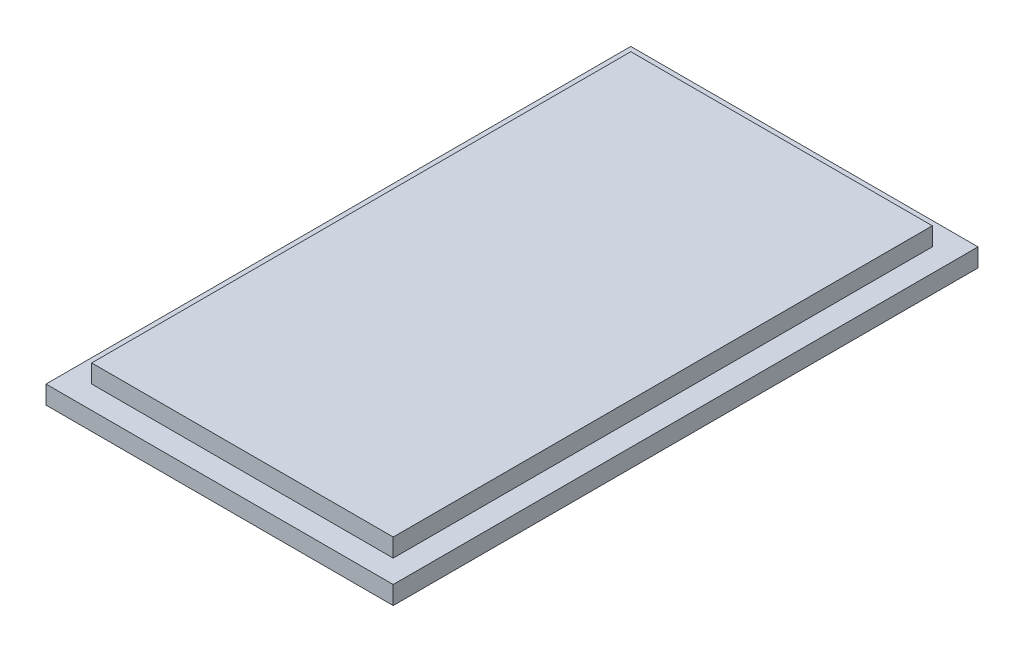
SolidWorks part; units mm, degrees
ref_plane "Alzado" through (0, 0, 0) normal (0, 0, 1) x (1, 0, 0)
ref_plane "Planta" through (0, 0, 0) normal (0, 1, 0) x (1, 0, 0)
ref_plane "Vista lateral" through (0, 0, 0) normal (1, 0, 0) x (0, 0, -1)
sketch "Croquis1" plane through (0, 0, 0) normal (0, 1, 0) x (1, 0, 0)
  line L0 (1.25, 1.25) -> (1.25, 30.75)
  line L1 (0, 0) -> (19, 0)
  line L2 (0, 0) -> (0, 32)
  line L3 (0, 32) -> (19, 32)
  line L4 (19, 0) -> (19, 32)
  line L5 (1.25, 30.75) -> (17.75, 30.75)
  line L6 (17.75, 1.25) -> (17.75, 30.75)
  line L7 (1.25, 1.25) -> (17.75, 1.25)
  dimension "D1" = 32
  dimension "D2" = 19
  dimension "D3" = 1.25
extrude "Saliente-Extruir1" add sketch "Croquis1" along normal blind 1
extrude "Saliente-Extruir2" add sketch "Croquis1<2>" along normal blind 2 contours L0 L7 L6 L5 region at (9.5, 0, -16)
sketch "Croquis1<2>" plane through (0, 0, 0) normal (0, 1, 0) x (1, 0, 0) same geometry as "Croquis1"
